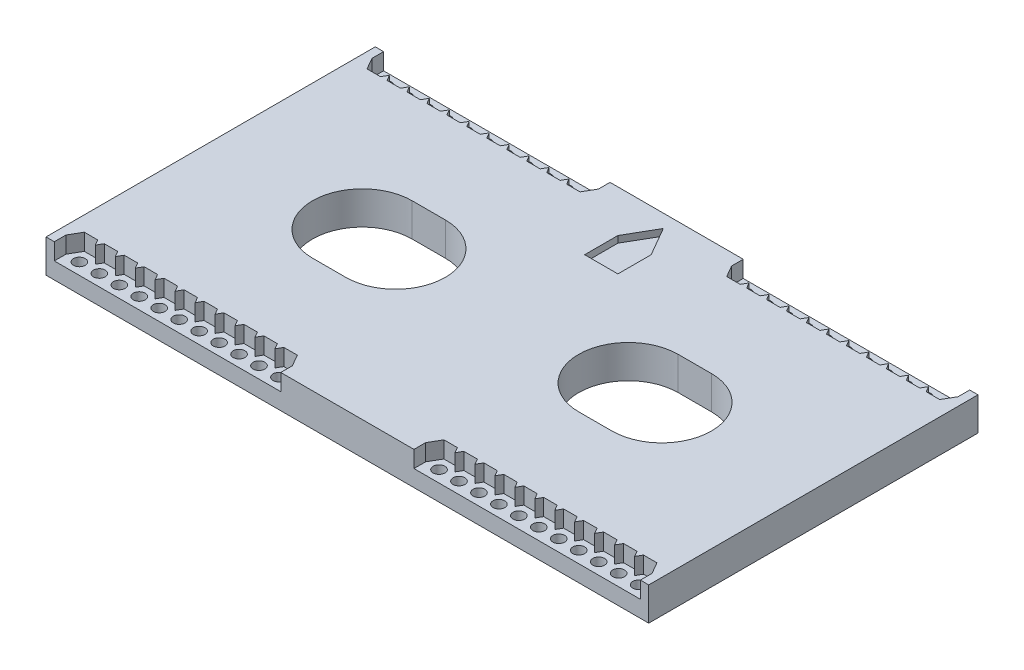
SolidWorks part; units mm, degrees
ref_plane "Front Plane" through (0, 0, 0) normal (0, 0, 1) x (1, 0, 0)
ref_plane "Top Plane" through (0, 0, 0) normal (0, 1, 0) x (1, 0, 0)
ref_plane "Right Plane" through (0, 0, 0) normal (1, 0, 0) x (0, 0, -1)
sketch "Sketch1" plane through (0, 0, 0) normal (0, 1, 0) x (1, 0, 0)
  line L0 (0, 58.42) -> (0, -58.42) construction
  line L1 (80.01, 56.1355) -> (81.329, 58.42)
  line L2 (-5.0555, 53.9782) -> (-3.81, 56.1355)
  line L3 (-5.0555, 53.9782) -> (106.7594, 53.9782)
  line L4 (-5.0555, 53.9782) -> (-5.0555, 0)
  line L5 (-5.0555, 0) -> (106.7594, 0)
  line L6 (106.7594, 53.9782) -> (106.7594, 0)
  line L7 (-3.81, 56.1355) -> (-2.5645, 53.9782)
  line L8 (0, 58.42) -> (-3.8467, 56.1991) construction
  line L9 (0, 58.42) -> (3.81, 58.42) construction
  line L10 (3.81, 58.42) -> (7.62, 58.42) construction
  line L11 (7.62, 58.42) -> (7.62, 53.9782) construction
  line L12 (0, 58.42) -> (-3.81, 58.42) construction
  line L13 (2.5645, 53.9782) -> (3.81, 56.1355)
  line L14 (3.81, 56.1355) -> (5.0555, 53.9782)
  line L15 (10.1845, 53.9782) -> (11.43, 56.1355)
  line L16 (11.43, 56.1355) -> (12.6755, 53.9782)
  line L17 (17.8045, 53.9782) -> (19.05, 56.1355)
  line L18 (19.05, 56.1355) -> (20.2955, 53.9782)
  line L19 (25.4245, 53.9782) -> (26.67, 56.1355)
  line L20 (26.67, 56.1355) -> (27.9155, 53.9782)
  line L21 (33.0445, 53.9782) -> (34.29, 56.1355)
  line L22 (34.29, 56.1355) -> (35.5355, 53.9782)
  line L23 (40.6645, 53.9782) -> (41.91, 56.1355)
  line L24 (41.91, 56.1355) -> (43.1555, 53.9782)
  line L25 (48.2845, 53.9782) -> (49.53, 56.1355)
  line L26 (49.53, 56.1355) -> (50.7755, 53.9782)
  line L27 (55.9045, 53.9782) -> (57.15, 56.1355)
  line L28 (57.15, 56.1355) -> (58.3955, 53.9782)
  line L29 (-3.81, 56.1355) -> (3.81, 56.1355) construction
  line L30 (7.62, 58.42) -> (15.24, 58.42) construction
  line L31 (106.7594, 62.8618) -> (106.7594, 53.9782)
  line L32 (81.329, 58.42) -> (81.329, 62.8618)
  line L33 (49.6094, 0) -> (62.3094, 0) construction
  line L34 (49.6094, 19) -> (62.3094, 19)
  line L35 (49.6094, -19) -> (62.3094, -19)
  line L53 (-8.304, 62.8618) -> (106.7594, 62.8618)
  line L54 (15.24, 62.8618) -> (15.24, 53.9782) construction
  line L55 (-5.129, 62.8618) -> (-5.129, 58.42)
  line L56 (-8.304, 62.8618) -> (-8.304, 0)
  line L57 (63.5245, 53.9782) -> (64.77, 56.1355)
  line L61 (-5.0555, 0) -> (-8.304, 0)
  line L67 (-5.129, 58.42) -> (-3.8467, 56.1991)
  line L68 (-3.8467, 56.1991) -> (-3.81, 56.1355)
  line L69 (64.77, 56.1355) -> (66.0155, 53.9782)
  line L70 (71.1445, 53.9782) -> (72.39, 56.1355)
  line L71 (72.39, 56.1355) -> (73.6355, 53.9782)
  line L72 (78.7645, 53.9782) -> (80.01, 56.1355)
  line L73 (80.01, 56.1355) -> (81.2555, 53.9782)
  circle A0 centre (0, 58.42) radius 2.2479
  circle A1 centre (0, -58.42) radius 2.2479 construction
  circle A2 centre (7.62, 58.42) radius 2.2479
  circle A3 centre (7.62, -58.42) radius 2.2479 construction
  circle A4 centre (15.24, 58.42) radius 2.2479
  circle A5 centre (15.24, -58.42) radius 2.2479 construction
  circle A6 centre (22.86, 58.42) radius 2.2479
  circle A7 centre (22.86, -58.42) radius 2.2479 construction
  circle A8 centre (30.48, 58.42) radius 2.2479
  circle A9 centre (30.48, -58.42) radius 2.2479 construction
  circle A10 centre (38.1, 58.42) radius 2.2479
  circle A11 centre (38.1, -58.42) radius 2.2479 construction
  circle A12 centre (45.72, 58.42) radius 2.2479
  circle A13 centre (45.72, -58.42) radius 2.2479 construction
  circle A14 centre (53.34, 58.42) radius 2.2479
  circle A15 centre (53.34, -58.42) radius 2.2479 construction
  circle A35 centre (60.96, 58.42) radius 2.2479
  circle A36 centre (60.96, -58.42) radius 2.2479 construction
  circle A37 centre (68.58, 58.42) radius 2.2479
  circle A38 centre (68.58, -58.42) radius 2.2479 construction
  circle A39 centre (76.2, 58.42) radius 2.2479
  circle A40 centre (76.2, -58.42) radius 2.2479 construction
  arc A42 (49.6094, 19) -> (49.6094, -19) centre (49.6094, 0) ccw
  arc A43 (62.3094, -19) -> (62.3094, 19) centre (62.3094, 0) ccw
  point P4 (0, 0)
  point P42 (55.9594, 0)
  point P79 (3.81, 58.42)
  dimension "D1" = 116.84
  dimension "D2" = 4.4958
  dimension "D5" = 57.15
  dimension "D8" = 12.7
  dimension "D6" = 49.6094
  dimension "D7" = 19
  dimension "D4" = 7.62
  dimension "D9" = 4.4418
  dimension "D10" = 120
  dimension "D11" = 12
  dimension "D16" = 3.175
  dimension "D3" = 11
extrude "Boss-Extrude1" add sketch "Sketch1" against normal blind 12.6625 contours L6 | A43 L5 L6 L3 L4 A42 L34 | L68 L67 L55 L53 L56 L61 L4 L2 | L3 L72 L1 L32 L53 L55 L67 L68 L7 L13 L14 L15 L16 L17 L18 L19 L20 L21 L22 L23 L24 L25 L26 L27 L28 L57 L69 L70 L71 A39 A37 A35 A14 A12 A10 | L7 L2 L3 | L14 L13 L3 | L16 L15 L3 | L18 L17 L3 | L20 L19 L3 | L22 L21 L3 | L24 L23 L3 | L26 L25 L3 | L28 L27 L3 | L69 L57 L3 | L71 L70 L3 | L73 L72 L3 | L1 L73 L3 L31 L53 L32 region at (78.6346, 0, -55.4914) region at (80.01, 0, -54.6973) region at (93.8713, 0, -58.39) region at (50.0621, 0, -29.8495) region at (72.39, 0, -54.6973) region at (-6.6558, 0, -31.7055) region at (64.77, 0, -54.6973) region at (-3.81, 0, -54.6973) region at (57.15, 0, -54.6973) region at (3.81, 0, -54.6973) region at (49.53, 0, -54.6973) region at (11.43, 0, -54.6973) region at (41.91, 0, -54.6973) region at (19.05, 0, -54.6973) region at (34.29, 0, -54.6973) region at (26.67, 0, -54.6973)
extrude "Cut-Extrude1" cut sketch "Sketch1<5>" against normal blind 6.35 contours L4 L2 L7 L3 L13 L14 L15 L16 L17 L18 L19 L20 L21 L22 L23 L24 L25 L26 L27 L53 L56 A14 A12 A10 A8 A6 A4 A2 region at (78.6346, 0, -55.4914)
sketch "Sketch1<5>" plane through (0, 0, 0) normal (0, 1, 0) x (1, 0, 0) same geometry as "Sketch1"
mirror "Mirror1" about plane through (0, 0, 0) normal (0, 0, 1) of bodies 102
mirror "Mirror2" about plane through (106.7594, -12.6625, 0) normal (-1, 0, 0) of bodies 103
sketch "Sketch4" plane through (0, 0, 0) normal (0, 1, 0) x (1, 0, 0)
  line L0 (100.4094, 46.7833) -> (106.7594, 57.7818)
  line L1 (106.7594, 57.7818) -> (113.1094, 46.7833)
  line L2 (113.1094, 46.7833) -> (100.4094, 46.7833)
  line L4 (81.329, 62.8618) -> (132.1898, 62.8618) construction
  line L6 (100.4094, 46.7833) -> (113.1094, 46.7833)
  line L7 (100.4094, 46.7833) -> (100.4094, 34.0833)
  line L8 (100.4094, 34.0833) -> (113.1094, 34.0833)
  line L9 (113.1094, 46.7833) -> (113.1094, 34.0833)
  point P3 (106.7594, 62.8618)
  point P4 (110.3198, 30.2733)
  point P5 (0, 0)
  dimension "D1" = 12.7
  dimension "D2" = 5.08
extrude "Cut-Extrude3" cut sketch "Sketch4" against normal blind 2.54 contours L9 L2 L7 L8 | L2 L1 L0 region at (106.7594, 0, -50.4495) region at (106.7594, 0, -40.4333)
